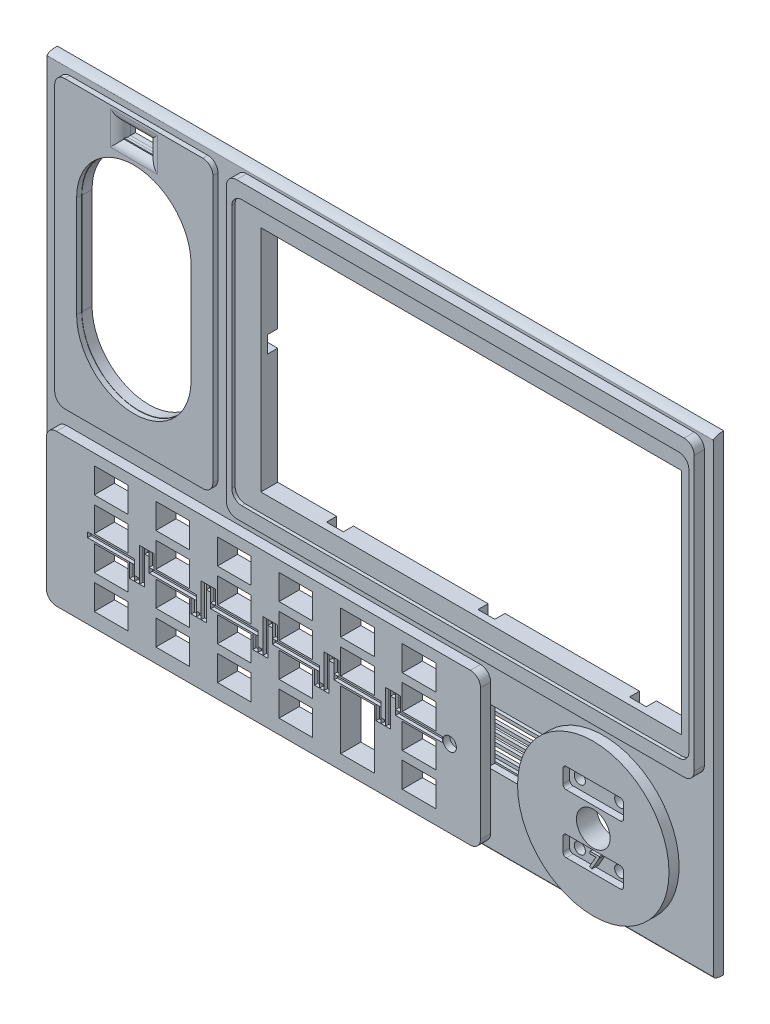
SolidWorks part; units mm, degrees
ref_plane "Front Plane" through (0, 0, 0) normal (0, 0, 1) x (1, 0, 0)
ref_plane "Top Plane" through (0, 0, 0) normal (0, 1, 0) x (1, 0, 0)
ref_plane "Right Plane" through (0, 0, 0) normal (1, 0, 0) x (0, 0, -1)
sketch "Sketch1" plane through (0, 0, 0) normal (0, 0, 1) x (1, 0, 0)
  line L1 (99, -70) -> (-99, -70)
  line L2 (99, -70) -> (99, 70)
  line L3 (99, 70) -> (-99, 70)
  line L4 (-99, -70) -> (-99, 70)
  line L5 (99, -70) -> (-99, 70) construction
  line L6 (99, 70) -> (-99, -70) construction
  point P0 (0, 0)
  dimension "D1" = 198
  dimension "D2" = 140
extrude "main_body" add sketch "Sketch1" along normal blind 3
fillet "long_corners" radius 3 2 edges at (0, 70, 3) (0, -70, 3) second distance 1 first distance on face at (0, 70, 1.5) first distance on face at (0, -70, 1.5)
sketch "Sketch2" plane through (0, 0, 3) normal (0, 0, 1) x (1, 0, 0)
  line L0 (-99, 24.75) -> (99, 24.75) construction
  line L1 (-99, 69) -> (-99, -69) construction
  line L2 (99, -69) -> (99, 69) construction
  line L3 (99, 69) -> (-99, 69) construction
  line L4 (-48.25, -17.75) -> (-95.25, -17.75)
  line L5 (-48.25, -17.75) -> (-48.25, 67.25)
  line L6 (-48.25, 67.25) -> (-95.25, 67.25)
  line L7 (-95.25, -17.75) -> (-95.25, 67.25)
  line L8 (-48.25, -17.75) -> (-95.25, 67.25) construction
  line L9 (-48.25, 67.25) -> (-95.25, -17.75) construction
  point P6 (-71.75, 24.75)
  dimension "D1" = 85
  dimension "D2" = 47
  dimension "D3" = 27.25
  dimension "D4" = 44.25
extrude "speaker" add sketch "Sketch2" along normal blind 1.5
fillet "speaker_corners" radius 3 4 edges at (-95.25, 67.25, 3.75) (-95.25, -17.75, 3.75) (-48.25, -17.75, 3.75) (-48.25, 67.25, 3.75)
sketch "Sketch19" plane through (0, 0, 4.5) normal (0, 0, 1) x (1, 0, 0)
  line L0 (-71.75, 67.25) -> (-71.75, -17.75) construction
  line L1 (-51.25, 67.25) -> (-92.25, 67.25) construction
  line L2 (-92.25, -17.75) -> (-51.25, -17.75) construction
  line L3 (-71.75, 8.25) -> (-71.75, 38.25) construction
  line L4 (-95.25, 64.25) -> (-95.25, -14.75) construction
  line L5 (-95.25, 24.75) -> (-48.25, 24.75) construction
  line L6 (-48.25, -14.75) -> (-48.25, 64.25) construction
  line L7 (-88.75, 8.25) -> (-88.75, 38.25)
  line L8 (-54.75, 8.25) -> (-54.75, 38.25)
  arc A0 (-88.75, 8.25) -> (-54.75, 8.25) centre (-71.75, 8.25) ccw
  arc A1 (-54.75, 38.25) -> (-88.75, 38.25) centre (-71.75, 38.25) ccw
  point P14 (-71.75, 23.25)
  point P19 (-71.75, -8.75)
  point P20 (-71.75, 55.25)
  dimension "D2" = 64
  dimension "D1" = 34
  dimension "D3" = 12
extrude "speaker_cut" cut sketch "Sketch19" against normal through all
sketch "Sketch21" plane through (0, 0, 0) normal (0, 0, -1) x (-1, 0, 0)
  line L0 (71.75, -8.75) -> (71.75, 55.25) construction
  line L2 (54.75, 8.25) -> (54.75, 38.25) construction
  line L3 (54.75, 23.25) -> (88.75, 23.25) construction
  line L4 (88.75, 38.25) -> (88.75, 8.25) construction
  line L5 (50.25, 59.25) -> (93.25, 59.25)
  line L6 (50.25, 59.25) -> (50.25, -12.75)
  line L7 (50.25, -12.75) -> (93.25, -12.75)
  line L8 (93.25, 59.25) -> (93.25, -12.75)
  line L9 (50.25, 59.25) -> (93.25, -12.75) construction
  line L10 (50.25, -12.75) -> (93.25, 59.25) construction
  arc A0 (54.75, 8.25) -> (88.75, 8.25) centre (71.75, 8.25) ccw construction
  arc A1 (88.75, 38.25) -> (54.75, 38.25) centre (71.75, 38.25) ccw construction
  point P14 (71.75, 23.25)
  dimension "D1" = 43
  dimension "D2" = 72
extrude "speaker_slot" cut sketch "Sketch21" against normal blind 3
sketch "Sketch36" plane through (0, 0, 3) normal (0, 0, -1) x (-1, 0, 0)
  line L0 (50.25, 23.25) -> (93.25, 23.25) construction
  line L1 (50.25, 59.25) -> (50.25, -12.75) construction
  line L2 (71.75, 8.2639) -> (71.75, 38.2361) construction
  line L3 (71.75, 8.2639) -> (71.75, 38.2361) construction
  line L4 (93.25, -12.75) -> (93.25, 59.25) construction
  line L5 (50.25, 59.25) -> (50.25, -12.75) construction
  line L6 (54.8316, 8.2639) -> (54.8316, 38.2361)
  line L9 (88.6684, 8.2639) -> (88.6684, 38.2361)
  line L10 (54.25, 8.2639) -> (54.25, 38.2361)
  line L11 (89.25, 8.2639) -> (89.25, 38.2361)
  line L12 (93.25, 59.25) -> (50.25, 59.25) construction
  line L13 (71.75, 59.25) -> (71.75, -12.75) construction
  line L14 (50.25, -12.75) -> (93.25, -12.75) construction
  line L23 (50.25, 57.25) -> (93.25, 57.25)
  line L25 (50.25, 57.25) -> (50.25, 56.75)
  line L26 (93.25, -0.25) -> (87.75, -0.25)
  line L27 (50.25, 56.75) -> (93.25, 56.75)
  line L28 (93.25, 57.25) -> (93.25, 56.75)
  line L37 (93.25, -12.75) -> (93.25, 59.25) construction
  line L38 (93.25, -0.25) -> (93.25, 0.25)
  line L39 (93.25, 0.25) -> (87.75, 0.25)
  line L48 (93.25, -10.75) -> (50.25, -10.75)
  line L49 (93.25, -10.75) -> (93.25, -10.25)
  line L50 (93.25, -10.25) -> (50.25, -10.25)
  line L51 (50.25, -10.75) -> (50.25, -10.25)
  line L52 (93.25, 46.75) -> (87.75, 46.75)
  line L53 (93.25, 46.75) -> (93.25, 46.25)
  line L54 (93.25, 46.25) -> (87.75, 46.25)
  line L55 (87.75, 46.75) -> (87.75, 46.25)
  line L56 (93.25, 35.25) -> (89.75, 35.25)
  line L57 (93.25, 35.25) -> (93.25, 34.75)
  line L58 (93.25, 34.75) -> (89.75, 34.75)
  line L59 (89.75, 35.25) -> (89.75, 34.75)
  line L60 (93.25, 23.25) -> (89.75, 23.25)
  line L61 (93.25, 23.25) -> (93.25, 23.75)
  line L62 (93.25, 23.75) -> (89.75, 23.75)
  line L63 (89.75, 23.25) -> (89.75, 23.75)
  line L64 (93.25, 10.75) -> (89.75, 10.75)
  line L65 (93.25, 10.75) -> (93.25, 11.25)
  line L66 (93.25, 11.25) -> (89.75, 11.25)
  line L67 (89.75, 10.75) -> (89.75, 11.25)
  line L68 (87.75, -0.25) -> (87.75, 0.25)
  line L69 (93.25, -5.25) -> (83.25, -5.25)
  line L70 (93.25, -5.25) -> (93.25, -5.75)
  line L71 (93.25, -5.75) -> (83.25, -5.75)
  line L72 (83.25, -5.25) -> (83.25, -5.75)
  line L73 (93.25, 52.25) -> (83.25, 52.25)
  line L74 (93.25, 52.25) -> (93.25, 51.75)
  line L75 (93.25, 51.75) -> (83.25, 51.75)
  line L76 (83.25, 52.25) -> (83.25, 51.75)
  line L77 (50.25, 52.25) -> (60.25, 52.25)
  line L78 (50.25, 52.25) -> (50.25, 51.75)
  line L79 (50.25, 51.75) -> (60.25, 51.75)
  line L80 (60.25, 52.25) -> (60.25, 51.75)
  line L81 (50.25, 46.75) -> (55.75, 46.75)
  line L82 (50.25, 46.75) -> (50.25, 46.25)
  line L83 (50.25, 46.25) -> (55.75, 46.25)
  line L84 (55.75, 46.75) -> (55.75, 46.25)
  line L85 (50.25, 35.25) -> (53.75, 35.25)
  line L86 (50.25, 35.25) -> (50.25, 34.75)
  line L87 (50.25, 34.75) -> (53.75, 34.75)
  line L88 (53.75, 35.25) -> (53.75, 34.75)
  line L89 (50.25, 23.25) -> (53.75, 23.25)
  line L90 (50.25, 23.25) -> (50.25, 23.75)
  line L91 (50.25, 23.75) -> (53.75, 23.75)
  line L92 (53.75, 23.25) -> (53.75, 23.75)
  line L93 (50.25, 10.25) -> (53.75, 10.25)
  line L94 (50.25, 10.25) -> (50.25, 10.75)
  line L95 (50.25, 10.75) -> (53.75, 10.75)
  line L96 (53.75, 10.25) -> (53.75, 10.75)
  line L97 (50.25, -0.25) -> (55.75, -0.25)
  line L98 (50.25, -0.25) -> (50.25, 0.25)
  line L99 (50.25, 0.25) -> (55.75, 0.25)
  line L100 (55.75, -0.25) -> (55.75, 0.25)
  line L101 (50.25, -5.25) -> (60.25, -5.25)
  line L102 (50.25, -5.25) -> (50.25, -5.75)
  line L103 (50.25, -5.75) -> (60.25, -5.75)
  line L104 (60.25, -5.25) -> (60.25, -5.75)
  arc A0 (54.25, 8.2639) -> (89.25, 8.2639) centre (71.75, 8.2639) ccw
  arc A1 (89.25, 38.2361) -> (54.25, 38.2361) centre (71.75, 38.2361) ccw
  arc A4 (54.8316, 8.2639) -> (88.6684, 8.2639) centre (71.75, 8.2639) ccw
  arc A5 (88.6684, 38.2361) -> (54.8316, 38.2361) centre (71.75, 38.2361) ccw
  point P6 (71.75, 23.25)
  point P22 (71.75, 23.25)
  point P31 (89.25, 23.25)
  point P32 (71.75, 55.1546)
  point P33 (71.75, -8.6546)
  point P95 (52, 35.25)
  point P96 (55.25, 51.75)
  point P97 (91.5, 10.75)
  dimension "D48" = 0.5816
  dimension "D1" = 33.8368
  dimension "D2" = 35
  dimension "D3" = 63.8091
  dimension "D4" = 0.5
  dimension "D5" = 0.5
  dimension "D6" = 0.5
  dimension "D7" = 0.5
  dimension "D8" = 0.5
  dimension "D9" = 11
  dimension "D10" = 11
  dimension "D11" = 5
  dimension "D12" = 4.5
  dimension "D13" = 10
  dimension "D14" = 5.5
  dimension "D15" = 3.5
  dimension "D16" = 3.5
  dimension "D17" = 0.5
  dimension "D18" = 0.5
  dimension "D19" = 0.5
  dimension "D20" = 0.5
  dimension "D21" = 11
  dimension "D22" = 11
  dimension "D23" = 5
  dimension "D24" = 10
  dimension "D25" = 5.5
  dimension "D26" = 3.5
  dimension "D27" = 3.5
  dimension "D28" = 0.5
  dimension "D29" = 0.5
  dimension "D30" = 0.5
  dimension "D31" = 0.5
  dimension "D32" = 0.5
  dimension "D33" = 0.5
  dimension "D34" = 0.5
  dimension "D35" = 12
  dimension "D36" = 10.5
  dimension "D37" = 5.5
  dimension "D38" = 5
  dimension "D39" = 4.5
  dimension "D40" = 3.5
  dimension "D41" = 10
  dimension "D42" = 4.5
  dimension "D43" = 5
  dimension "D44" = 10
  dimension "D45" = 3.5
  dimension "D46" = 5.5
  dimension "D47" = 10
extrude "speaker_print_support" add sketch "Sketch36" along normal blind 3
sketch "Sketch3" plane through (0, 0, 3) normal (0, 0, 1) x (1, 0, 0)
  line L0 (-99, 24.625) -> (99, 24.625) construction
  line L1 (-99, 69) -> (-99, -69) construction
  line L2 (99, -69) -> (99, 69) construction
  line L4 (-48.25, -14.75) -> (-48.25, 64.25) construction
  line L5 (96.25, -19) -> (-42.75, -19)
  line L6 (96.25, -19) -> (96.25, 68.25)
  line L7 (96.25, 68.25) -> (-42.75, 68.25)
  line L8 (-42.75, -19) -> (-42.75, 68.25)
  line L9 (96.25, -19) -> (-42.75, 68.25) construction
  line L10 (96.25, 68.25) -> (-42.75, -19) construction
  line L11 (99, 70) -> (-99, 70) construction
  point P8 (26.75, 24.625)
  dimension "D1" = 1.75
  dimension "D2" = 87.25
  dimension "D3" = 139
  dimension "D4" = 2.75
  dimension "D5" = 5.5
extrude "lcd" add sketch "Sketch3" along normal blind 3
fillet "lcd_corners" radius 3 4 edges at (96.25, -19, 4.5) (-42.75, -19, 4.5) (96.25, 68.25, 4.5) (-42.75, 68.25, 4.5)
sketch "Sketch9" plane through (0, 0, 6) normal (0, 0, 1) x (1, 0, 0)
  line L0 (-42.75, 24.5) -> (96.25, 24.5) construction
  line L1 (-42.75, 65.25) -> (-42.75, -16) construction
  line L2 (96.25, -16) -> (96.25, 65.25) construction
  line L3 (-39.75, -19) -> (93.25, -19) construction
  line L4 (94.65, -14.875) -> (-41.15, -14.875)
  line L5 (94.65, -14.875) -> (94.65, 63.875)
  line L6 (94.65, 63.875) -> (-41.15, 63.875)
  line L7 (-41.15, -14.875) -> (-41.15, 63.875)
  line L8 (94.65, -14.875) -> (-41.15, 63.875) construction
  line L9 (94.65, 63.875) -> (-41.15, -14.875) construction
  line L10 (93.25, 68.25) -> (-39.75, 68.25) construction
  line L11 (96.25, -16) -> (96.25, 65.25) construction
  point P6 (26.75, 24.5)
  dimension "D1" = 135.8
  dimension "D2" = 78.75
  dimension "D3" = 1.6
  dimension "D4" = 4.125
  dimension "D5" = 4.375
  dimension "D6" = 1.6
extrude "lcd_front" cut sketch "Sketch9" against normal blind 1
fillet "lcd_front_corners" radius 3 4 edges at (94.65, -14.875, 5.5) (94.65, 63.875, 5.5) (-41.15, 63.875, 5.5) (-41.15, -14.875, 5.5)
sketch "Sketch10" plane through (0, 0, 0) normal (0, 0, -1) x (-1, 0, 0)
  line L0 (-94.65, -11.875) -> (-94.65, 60.875) construction
  line L1 (-91.65, 63.875) -> (38.15, 63.875) construction
  line L2 (41.15, 63.875) -> (41.15, -14.875) construction
  line L3 (-94.65, 63.875) -> (41.15, 63.875) construction
  line L4 (33.5, -9.5) -> (-91.5, -9.5)
  line L5 (33.5, -9.5) -> (33.5, 58.5)
  line L6 (33.5, 58.5) -> (-91.5, 58.5)
  line L7 (-91.5, -9.5) -> (-91.5, 58.5)
  line L8 (-91.5, -9.5) -> (33.5, 58.5) construction
  line L9 (-91.5, 58.5) -> (33.5, -9.5) construction
  line L10 (-99, -70) -> (-99, 70) construction
  line L11 (-99, 70) -> (99, 70) construction
  line L13 (38.15, -14.875) -> (-91.65, -14.875) construction
  dimension "D1" = 125
  dimension "D2" = 68
  dimension "D3" = 7.5
  dimension "D4" = 7.65
  dimension "D5" = 11.5
  dimension "D6" = 5.375
  dimension "D7" = 3.15
  dimension "D8" = 5.375
  dimension "D9" = 5.375
extrude "lcd_back" cut sketch "Sketch10" against normal through all
sketch "Sketch56" plane through (0, 0, 0) normal (0, 0, -1) x (-1, 0, 0)
  line L0 (-91.5, -9.5) -> (33.5, -9.5) construction
  line L1 (-79, -9.5) -> (-74, -9.5)
  line L2 (-79, -9.5) -> (-79, -12.5)
  line L3 (-79, -12.5) -> (-74, -12.5)
  line L4 (-74, -9.5) -> (-74, -12.5)
  line L5 (33.5, 58.5) -> (-91.5, 58.5) construction
  line L6 (-34, -9.5) -> (-29, -9.5)
  line L7 (-34, -9.5) -> (-34, -12.5)
  line L8 (-34, -12.5) -> (-29, -12.5)
  line L9 (-29, -9.5) -> (-29, -12.5)
  line L10 (11, -9.5) -> (16, -9.5)
  line L11 (11, -9.5) -> (11, -12.5)
  line L12 (11, -12.5) -> (16, -12.5)
  line L13 (16, -9.5) -> (16, -12.5)
  line L14 (-79, 58.5) -> (-74, 58.5)
  line L15 (-79, 58.5) -> (-79, 61.5)
  line L16 (-79, 61.5) -> (-74, 61.5)
  line L17 (-74, 58.5) -> (-74, 61.5)
  line L18 (33.5, -9.5) -> (33.5, 58.5) construction
  line L19 (-34, 58.5) -> (-29, 58.5)
  line L20 (-34, 58.5) -> (-34, 61.5)
  line L21 (-34, 61.5) -> (-29, 61.5)
  line L22 (-29, 58.5) -> (-29, 61.5)
  line L23 (11, 58.5) -> (16, 58.5)
  line L24 (11, 58.5) -> (11, 61.5)
  line L25 (11, 61.5) -> (16, 61.5)
  line L26 (16, 58.5) -> (16, 61.5)
  line L27 (33.5, 30) -> (36.5, 30)
  line L28 (33.5, 30) -> (33.5, 25)
  line L29 (33.5, 25) -> (36.5, 25)
  line L30 (36.5, 30) -> (36.5, 25)
  line L31 (-99, -70) -> (-99, 70) construction
  line L32 (-99, 70) -> (99, 70) construction
  point P34 (-29, -11)
  dimension "D1" = 5
  dimension "D2" = 5
  dimension "D3" = 5
  dimension "D4" = 5
  dimension "D5" = 5
  dimension "D6" = 5
  dimension "D7" = 5
  dimension "D8" = 3
  dimension "D9" = 3
  dimension "D10" = 3
  dimension "D11" = 3
  dimension "D12" = 3
  dimension "D13" = 3
  dimension "D14" = 3
  dimension "D15" = 40
  dimension "D16" = 40
  dimension "D17" = 20
  dimension "D18" = 20
  dimension "D19" = 40
  dimension "D20" = 40
  dimension "D21" = 40
extrude "lcd_glue_points" cut sketch "Sketch56" against normal blind 3
sketch "Sketch4" plane through (0, 0, 3) normal (0, 0, 1) x (1, 0, 0)
  line L0 (-99, -45.75) -> (99, -45.75) construction
  line L1 (-99, 69) -> (-99, -69) construction
  line L2 (99, -69) -> (99, 69) construction
  line L4 (-92.25, -17.75) -> (-51.25, -17.75) construction
  line L5 (32.75, -68.25) -> (-96.25, -68.25)
  line L6 (32.75, -68.25) -> (32.75, -23.25)
  line L7 (32.75, -23.25) -> (-96.25, -23.25)
  line L8 (-96.25, -68.25) -> (-96.25, -23.25)
  line L9 (32.75, -68.25) -> (-96.25, -23.25) construction
  line L10 (32.75, -23.25) -> (-96.25, -68.25) construction
  line L11 (-99, -70) -> (99, -70) construction
  point P8 (-31.75, -45.75)
  dimension "D1" = 1.75
  dimension "D2" = 129
  dimension "D3" = 45
  dimension "D4" = 2.75
  dimension "D5" = 5.5
extrude "keypad" add sketch "Sketch4" along normal blind 3
fillet "keypad_corners" radius 3 4 edges at (-96.25, -68.25, 4.5) (32.75, -68.25, 4.5) (32.75, -23.25, 4.5) (-96.25, -23.25, 4.5)
sketch "Sketch25" plane through (0, 0, 6) normal (0, 0, 1) x (1, 0, 0)
  line L0 (-96.25, -30.25) -> (32.75, -30.25) construction
  line L1 (29.75, -23.25) -> (-93.25, -23.25) construction
  line L2 (-93.25, -68.25) -> (29.75, -68.25) construction
  line L3 (-77, -23.25) -> (-77, -68.25) construction
  line L5 (-35.4, -64) -> (32.75, -64) construction
  line L6 (-96.25, -26.25) -> (-96.25, -65.25) construction
  line L11 (32.75, -65.25) -> (32.75, -26.25) construction
  line L12 (-58.7, -23.25) -> (-58.7, -68.25) construction
  line L13 (-96.25, -40.25) -> (32.75, -40.25) construction
  line L14 (29.75, -23.25) -> (-93.25, -23.25) construction
  line L15 (-40.4, -23.25) -> (-40.4, -68.25) construction
  line L16 (-93.25, -68.25) -> (29.75, -68.25) construction
  line L17 (-72, -34) -> (-82, -34)
  line L18 (-22.1, -23.25) -> (-22.1, -68.25) construction
  line L19 (-96.25, -50.25) -> (32.75, -50.25) construction
  line L20 (-3.8, -23.25) -> (-3.8, -68.25) construction
  line L21 (-72, -34) -> (-72, -26.5)
  line L22 (14.5, -23.25) -> (14.5, -68.25) construction
  line L23 (-96.25, -26.25) -> (-96.25, -65.25) construction
  line L24 (-96.25, -60.25) -> (32.75, -60.25) construction
  line L25 (-72, -26.5) -> (-82, -26.5)
  line L26 (-82, -34) -> (-82, -26.5)
  line L27 (-72, -34) -> (-82, -26.5) construction
  line L28 (-72, -26.5) -> (-82, -34) construction
  line L29 (-72, -44) -> (-82, -44)
  line L30 (-72, -44) -> (-72, -36.5)
  line L31 (-72, -36.5) -> (-82, -36.5)
  line L32 (-82, -44) -> (-82, -36.5)
  line L33 (-72, -44) -> (-82, -36.5) construction
  line L34 (-72, -36.5) -> (-82, -44) construction
  line L35 (-72, -54) -> (-82, -54)
  line L36 (-72, -54) -> (-72, -46.5)
  line L37 (-72, -46.5) -> (-82, -46.5)
  line L38 (-82, -54) -> (-82, -46.5)
  line L39 (-72, -54) -> (-82, -46.5) construction
  line L40 (-72, -46.5) -> (-82, -54) construction
  line L41 (-72, -64) -> (-82, -64)
  line L42 (-72, -64) -> (-72, -56.5)
  line L43 (-72, -56.5) -> (-82, -56.5)
  line L44 (-82, -64) -> (-82, -56.5)
  line L45 (-72, -64) -> (-82, -56.5) construction
  line L46 (-72, -56.5) -> (-82, -64) construction
  line L47 (-53.7, -34) -> (-63.7, -34)
  line L48 (-53.7, -34) -> (-53.7, -26.5)
  line L49 (-53.7, -26.5) -> (-63.7, -26.5)
  line L50 (-63.7, -34) -> (-63.7, -26.5)
  line L51 (-53.7, -34) -> (-63.7, -26.5) construction
  line L52 (-53.7, -26.5) -> (-63.7, -34) construction
  line L53 (-53.7, -44) -> (-63.7, -44)
  line L54 (-53.7, -44) -> (-53.7, -36.5)
  line L55 (-53.7, -36.5) -> (-63.7, -36.5)
  line L56 (-63.7, -44) -> (-63.7, -36.5)
  line L57 (-53.7, -44) -> (-63.7, -36.5) construction
  line L58 (-53.7, -36.5) -> (-63.7, -44) construction
  line L59 (-53.7, -54) -> (-63.7, -54)
  line L60 (-53.7, -54) -> (-53.7, -46.5)
  line L61 (-53.7, -46.5) -> (-63.7, -46.5)
  line L62 (-63.7, -54) -> (-63.7, -46.5)
  line L63 (-53.7, -54) -> (-63.7, -46.5) construction
  line L64 (-53.7, -46.5) -> (-63.7, -54) construction
  line L65 (-53.7, -64) -> (-63.7, -64)
  line L66 (-53.7, -64) -> (-53.7, -56.5)
  line L67 (-53.7, -56.5) -> (-63.7, -56.5)
  line L68 (-63.7, -64) -> (-63.7, -56.5)
  line L69 (-53.7, -64) -> (-63.7, -56.5) construction
  line L70 (-53.7, -56.5) -> (-63.7, -64) construction
  line L71 (-35.4, -34) -> (-45.4, -34)
  line L72 (-35.4, -34) -> (-35.4, -26.5)
  line L73 (-35.4, -26.5) -> (-45.4, -26.5)
  line L74 (-45.4, -34) -> (-45.4, -26.5)
  line L75 (-35.4, -34) -> (-45.4, -26.5) construction
  line L76 (-35.4, -26.5) -> (-45.4, -34) construction
  line L77 (-35.4, -44) -> (-45.4, -44)
  line L78 (-35.4, -44) -> (-35.4, -36.5)
  line L79 (-35.4, -36.5) -> (-45.4, -36.5)
  line L80 (-45.4, -44) -> (-45.4, -36.5)
  line L81 (-35.4, -44) -> (-45.4, -36.5) construction
  line L82 (-35.4, -36.5) -> (-45.4, -44) construction
  line L83 (-35.4, -54) -> (-45.4, -54)
  line L84 (-35.4, -54) -> (-35.4, -46.5)
  line L85 (-35.4, -46.5) -> (-45.4, -46.5)
  line L86 (-45.4, -54) -> (-45.4, -46.5)
  line L87 (-35.4, -54) -> (-45.4, -46.5) construction
  line L88 (-35.4, -46.5) -> (-45.4, -54) construction
  line L89 (-35.4, -64) -> (-45.4, -64)
  line L90 (-35.4, -64) -> (-35.4, -56.5)
  line L91 (-35.4, -56.5) -> (-45.4, -56.5)
  line L92 (-45.4, -64) -> (-45.4, -56.5)
  line L93 (-35.4, -64) -> (-45.4, -56.5) construction
  line L94 (-35.4, -56.5) -> (-45.4, -64) construction
  line L95 (-17.1, -34) -> (-27.1, -34)
  line L96 (-17.1, -34) -> (-17.1, -26.5)
  line L97 (-17.1, -26.5) -> (-27.1, -26.5)
  line L98 (-27.1, -34) -> (-27.1, -26.5)
  line L99 (-17.1, -34) -> (-27.1, -26.5) construction
  line L100 (-17.1, -26.5) -> (-27.1, -34) construction
  line L101 (-17.1, -44) -> (-27.1, -44)
  line L102 (-17.1, -44) -> (-17.1, -36.5)
  line L103 (-17.1, -36.5) -> (-27.1, -36.5)
  line L104 (-27.1, -44) -> (-27.1, -36.5)
  line L105 (-17.1, -44) -> (-27.1, -36.5) construction
  line L106 (-17.1, -36.5) -> (-27.1, -44) construction
  line L111 (-17.1, -54) -> (-27.1, -54)
  line L112 (-17.1, -54) -> (-17.1, -46.5)
  line L113 (-17.1, -46.5) -> (-27.1, -46.5)
  line L114 (-27.1, -54) -> (-27.1, -46.5)
  line L115 (-17.1, -54) -> (-27.1, -46.5) construction
  line L116 (-17.1, -46.5) -> (-27.1, -54) construction
  line L117 (-17.1, -64) -> (-27.1, -64)
  line L118 (-17.1, -64) -> (-17.1, -56.5)
  line L119 (-17.1, -56.5) -> (-27.1, -56.5)
  line L120 (-27.1, -64) -> (-27.1, -56.5)
  line L121 (-17.1, -64) -> (-27.1, -56.5) construction
  line L122 (-17.1, -56.5) -> (-27.1, -64) construction
  line L127 (1.2, -34) -> (-8.8, -34)
  line L128 (1.2, -34) -> (1.2, -26.5)
  line L129 (1.2, -26.5) -> (-8.8, -26.5)
  line L130 (-8.8, -34) -> (-8.8, -26.5)
  line L131 (1.2, -34) -> (-8.8, -26.5) construction
  line L132 (1.2, -26.5) -> (-8.8, -34) construction
  line L133 (19.5, -34) -> (9.5, -34)
  line L134 (19.5, -34) -> (19.5, -26.5)
  line L135 (19.5, -26.5) -> (9.5, -26.5)
  line L136 (9.5, -34) -> (9.5, -26.5)
  line L137 (19.5, -34) -> (9.5, -26.5) construction
  line L138 (19.5, -26.5) -> (9.5, -34) construction
  line L139 (1.2, -44) -> (-8.8, -44)
  line L140 (1.2, -44) -> (1.2, -36.5)
  line L141 (1.2, -36.5) -> (-8.8, -36.5)
  line L142 (-8.8, -44) -> (-8.8, -36.5)
  line L143 (1.2, -44) -> (-8.8, -36.5) construction
  line L144 (1.2, -36.5) -> (-8.8, -44) construction
  line L145 (19.5, -44) -> (9.5, -44)
  line L146 (19.5, -44) -> (19.5, -36.5)
  line L147 (19.5, -36.5) -> (9.5, -36.5)
  line L148 (9.5, -44) -> (9.5, -36.5)
  line L149 (19.5, -44) -> (9.5, -36.5) construction
  line L150 (19.5, -36.5) -> (9.5, -44) construction
  line L151 (19.5, -54) -> (9.5, -54)
  line L152 (19.5, -54) -> (19.5, -46.5)
  line L153 (19.5, -46.5) -> (9.5, -46.5)
  line L154 (9.5, -54) -> (9.5, -46.5)
  line L155 (19.5, -54) -> (9.5, -46.5) construction
  line L156 (19.5, -46.5) -> (9.5, -54) construction
  line L157 (19.5, -64) -> (9.5, -64)
  line L158 (19.5, -64) -> (19.5, -56.5)
  line L159 (19.5, -56.5) -> (9.5, -56.5)
  line L160 (9.5, -64) -> (9.5, -56.5)
  line L161 (19.5, -64) -> (9.5, -56.5) construction
  line L162 (19.5, -56.5) -> (9.5, -64) construction
  line L163 (1.2, -64) -> (-8.8, -64)
  line L164 (1.2, -64) -> (1.2, -46.5)
  line L165 (1.2, -46.5) -> (-8.8, -46.5)
  line L166 (-8.8, -64) -> (-8.8, -46.5)
  line L167 (1.2, -64) -> (-8.8, -46.5) construction
  line L168 (1.2, -46.5) -> (-8.8, -64) construction
  point P34 (-77, -30.25)
  point P39 (-77, -40.25)
  point P44 (-77, -50.25)
  point P49 (-77, -60.25)
  point P54 (-58.7, -30.25)
  point P59 (-58.7, -40.25)
  point P64 (-58.7, -50.25)
  point P69 (-58.7, -60.25)
  point P74 (-40.4, -30.25)
  point P79 (-40.4, -40.25)
  point P84 (-40.4, -50.25)
  point P89 (-40.4, -60.25)
  point P94 (-22.1, -30.25)
  point P99 (-22.1, -40.25)
  point P104 (-22.1, -50.25)
  point P109 (-22.1, -60.25)
  point P114 (-3.8, -30.25)
  point P119 (14.5, -30.25)
  point P124 (-3.8, -40.25)
  point P129 (14.5, -40.25)
  point P134 (14.5, -50.25)
  point P139 (14.5, -60.25)
  point P144 (-3.8, -55.25)
  dimension "D1" = 18.25
  dimension "D2" = 18.3
  dimension "D3" = 18.3
  dimension "D4" = 18.3
  dimension "D5" = 18.3
  dimension "D6" = 18.3
  dimension "D7" = 19.25
  dimension "D8" = 7
  dimension "D9" = 10
  dimension "D10" = 10
  dimension "D11" = 10
  dimension "D12" = 8
  dimension "D13" = 10
  dimension "D14" = 10
  dimension "D15" = 10
  dimension "D16" = 10
  dimension "D17" = 10
  dimension "D18" = 10
  dimension "D19" = 10
  dimension "D20" = 10
  dimension "D21" = 10
  dimension "D22" = 10
  dimension "D23" = 10
  dimension "D24" = 10
  dimension "D25" = 10
  dimension "D26" = 10
  dimension "D27" = 10
  dimension "D28" = 10
  dimension "D29" = 10
  dimension "D30" = 10
  dimension "D31" = 10
  dimension "D32" = 10
  dimension "D33" = 10
  dimension "D34" = 10
  dimension "D35" = 10
  dimension "D36" = 7.5
  dimension "D37" = 7.5
  dimension "D38" = 7.5
  dimension "D39" = 7.5
  dimension "D40" = 7.5
  dimension "D41" = 7.5
  dimension "D42" = 17.5
  dimension "D43" = 7.5
  dimension "D44" = 7.5
  dimension "D45" = 7.5
  dimension "D46" = 7.5
  dimension "D47" = 7.5
  dimension "D48" = 7.5
  dimension "D49" = 7.5
  dimension "D50" = 7.5
  dimension "D51" = 7.5
  dimension "D52" = 7.5
  dimension "D53" = 7.5
  dimension "D54" = 7.5
  dimension "D55" = 7.5
  dimension "D56" = 7.5
  dimension "D57" = 7.5
  dimension "D58" = 7.5
  dimension "D59" = 5
extrude "keypad_cuts_0.8" cut sketch "Sketch25" against normal through all
sketch "Sketch40" plane through (0, 0, 6) normal (0, 0, 1) x (1, 0, 0)
  line L0 (16.75, -23.25) -> (16.75, -68.25) construction
  line L1 (-8.25, -23.25) -> (-8.25, -68.25) construction
  line L2 (-67.25, -23.25) -> (-67.25, -68.25) construction
  line L3 (-96.25, -45.75) -> (32.75, -45.75) construction
  line L4 (-83.25, -23.25) -> (-83.25, -68.25) construction
  line L5 (29.75, -23.25) -> (-93.25, -23.25) construction
  line L6 (-93.25, -68.25) -> (29.75, -68.25) construction
  line L11 (-77.25, -49.75) -> (-89.25, -49.75)
  line L12 (-77.25, -49.75) -> (-77.25, -41.75)
  line L13 (-93.25, -68.25) -> (29.75, -68.25) construction
  line L14 (-77.25, -41.75) -> (-89.25, -41.75)
  line L15 (-89.25, -49.75) -> (-89.25, -41.75)
  line L16 (-35.25, -68.25) -> (-35.25, -23.25) construction
  line L18 (29.75, -23.25) -> (-93.25, -23.25) construction
  line L19 (-77.25, -49.75) -> (-89.25, -41.75) construction
  line L20 (-51.25, -68.25) -> (-51.25, -23.25) construction
  line L22 (-77.25, -41.75) -> (-89.25, -49.75) construction
  line L23 (-61.25, -49.75) -> (-73.25, -49.75)
  line L24 (-61.25, -49.75) -> (-61.25, -41.75)
  line L25 (-61.25, -41.75) -> (-73.25, -41.75)
  line L26 (-73.25, -49.75) -> (-73.25, -41.75)
  line L27 (-61.25, -49.75) -> (-73.25, -41.75) construction
  line L28 (-61.25, -41.75) -> (-73.25, -49.75) construction
  line L29 (-45.25, -49.75) -> (-57.25, -49.75)
  line L30 (-45.25, -49.75) -> (-45.25, -41.75)
  line L31 (-45.25, -41.75) -> (-57.25, -41.75)
  line L32 (-57.25, -49.75) -> (-57.25, -41.75)
  line L33 (-45.25, -49.75) -> (-57.25, -41.75) construction
  line L34 (-45.25, -41.75) -> (-57.25, -49.75) construction
  line L35 (-29.25, -49.75) -> (-41.25, -49.75)
  line L36 (-29.25, -49.75) -> (-29.25, -41.75)
  line L37 (-29.25, -41.75) -> (-41.25, -41.75)
  line L38 (-41.25, -49.75) -> (-41.25, -41.75)
  line L39 (-29.25, -49.75) -> (-41.25, -41.75) construction
  line L40 (-29.25, -41.75) -> (-41.25, -49.75) construction
  line L45 (-2.25, -41.75) -> (-14.25, -41.75)
  line L46 (-2.25, -41.75) -> (-2.25, -33.75)
  line L51 (-2.25, -33.75) -> (-14.25, -33.75)
  line L52 (-14.25, -41.75) -> (-14.25, -33.75)
  line L53 (22.75, -35.75) -> (10.75, -35.75)
  line L54 (22.75, -35.75) -> (22.75, -27.75)
  line L55 (22.75, -27.75) -> (10.75, -27.75)
  line L56 (10.75, -35.75) -> (10.75, -27.75)
  line L57 (22.75, -35.75) -> (10.75, -27.75) construction
  line L58 (22.75, -27.75) -> (10.75, -35.75) construction
  line L59 (22.75, -63.75) -> (10.75, -63.75)
  line L60 (22.75, -63.75) -> (22.75, -55.75)
  line L61 (22.75, -55.75) -> (10.75, -55.75)
  line L62 (10.75, -63.75) -> (10.75, -55.75)
  line L63 (22.75, -63.75) -> (10.75, -55.75) construction
  line L64 (22.75, -55.75) -> (10.75, -63.75) construction
  line L69 (32.75, -65.25) -> (32.75, -26.25) construction
  line L70 (-2.25, -57.25) -> (-14.25, -57.25)
  line L75 (-2.25, -57.25) -> (-2.25, -49.25)
  line L76 (-2.25, -49.25) -> (-14.25, -49.25)
  line L77 (-2.25, -41.75) -> (-14.25, -33.75) construction
  line L78 (-2.25, -33.75) -> (-14.25, -41.75) construction
  line L85 (-14.25, -57.25) -> (-14.25, -49.25)
  line L86 (-2.25, -57.25) -> (-14.25, -49.25) construction
  line L87 (-2.25, -49.25) -> (-14.25, -57.25) construction
  line L88 (-96.25, -26.25) -> (-96.25, -65.25) construction
  line L89 (32.75, -65.25) -> (32.75, -26.25) construction
  line L93 (32.75, -59.75) -> (-96.25, -59.75) construction
  line L94 (-96.25, -31.75) -> (32.75, -31.75) construction
  line L95 (32.75, -31.75) -> (32.75, -37.75) construction
  line L96 (32.75, -37.75) -> (-96.25, -37.75) construction
  line L99 (-96.25, -26.25) -> (-96.25, -65.25) construction
  line L100 (-96.25, -53.75) -> (32.75, -53.75) construction
  point P18 (-83.25, -45.75)
  point P25 (-67.25, -45.75)
  point P30 (-51.25, -45.75)
  point P35 (-35.25, -45.75)
  point P40 (-8.25, -37.75)
  point P45 (-8.25, -53.25)
  point P50 (16.75, -31.75)
  point P55 (16.75, -59.75)
  dimension "D1" = 8
  dimension "D2" = 8
  dimension "D3" = 8
  dimension "D4" = 8
  dimension "D5" = 8
  dimension "D6" = 12
  dimension "D7" = 8
  dimension "D8" = 8
  dimension "D9" = 12
  dimension "D10" = 12
  dimension "D11" = 12
  dimension "D12" = 12
  dimension "D13" = 12
  dimension "D14" = 12
  dimension "D15" = 8
  dimension "D16" = 12
  dimension "D17" = 8
  dimension "D18" = 8
  dimension "D19" = 27
  dimension "D20" = 14
  dimension "D21" = 16
  dimension "D22" = 16
  dimension "D23" = 16
  dimension "D24" = 25
  dimension "D25" = 14
extrude "keypad_cuts_0.7" [suppressed] cut sketch "Sketch40" against normal through all
sketch "Sketch41" [suppressed] plane through (0, 0, 0) normal (0, 0, -1) x (-1, 0, 0)
  line L0 (-22.75, -27.75) -> (-10.75, -35.75) construction
  line L1 (-22.75, -55.75) -> (-10.75, -63.75) construction
  line L2 (8.25, -33.75) -> (8.25, -57.25) construction
  line L3 (-10.75, -63.75) -> (-22.75, -63.75) construction
  line L4 (29.25, -45.75) -> (89.25, -45.75) construction
  line L5 (29.25, -49.75) -> (29.25, -41.75) construction
  line L6 (89.25, -41.75) -> (89.25, -49.75) construction
  line L7 (-6.75, -39.75) -> (-26.75, -39.75)
  line L8 (2.25, -33.75) -> (14.25, -33.75) construction
  line L9 (-6.75, -39.75) -> (-6.75, -23.75)
  line L10 (91.25, -52.75) -> (27.25, -52.75)
  line L11 (-6.75, -23.75) -> (-26.75, -23.75)
  line L12 (14.25, -57.25) -> (2.25, -57.25) construction
  line L13 (-26.75, -39.75) -> (-26.75, -23.75)
  line L14 (-10.75, -55.75) -> (-22.75, -63.75) construction
  line L15 (-6.75, -39.75) -> (-26.75, -23.75) construction
  line L16 (-10.75, -35.75) -> (-22.75, -35.75) construction
  line L17 (-22.75, -35.75) -> (-22.75, -27.75) construction
  line L18 (-22.75, -35.75) -> (-10.75, -27.75) construction
  line L19 (-6.75, -23.75) -> (-26.75, -39.75) construction
  line L21 (-6.75, -67.75) -> (-26.75, -67.75)
  line L22 (16.25, -59.5) -> (0.25, -59.5)
  line L23 (-6.75, -67.75) -> (-6.75, -51.75)
  line L24 (91.25, -52.75) -> (91.25, -38.75)
  line L25 (-6.75, -51.75) -> (-26.75, -51.75)
  line L26 (91.25, -38.75) -> (27.25, -38.75)
  line L27 (-26.75, -67.75) -> (-26.75, -51.75)
  line L28 (27.25, -52.75) -> (27.25, -38.75)
  line L29 (-6.75, -67.75) -> (-26.75, -51.75) construction
  line L30 (91.25, -52.75) -> (27.25, -38.75) construction
  line L31 (-6.75, -51.75) -> (-26.75, -67.75) construction
  line L36 (16.25, -59.5) -> (16.25, -31.5)
  line L37 (16.25, -31.5) -> (0.25, -31.5)
  line L42 (0.25, -59.5) -> (0.25, -31.5)
  line L43 (16.25, -59.5) -> (0.25, -31.5) construction
  line L48 (91.25, -38.75) -> (27.25, -52.75) construction
  line L49 (16.25, -31.5) -> (0.25, -59.5) construction
  point P19 (59.25, -45.75)
  point P44 (8.25, -45.5)
  point P68 (-16.75, -59.75)
  point P69 (-16.75, -31.75)
  dimension "D1" = 20
  dimension "D2" = 20
  dimension "D3" = 16
  dimension "D4" = 16
  dimension "D5" = 16
  dimension "D6" = 28
  dimension "D7" = 64
  dimension "D8" = 14
extrude "keypad_back_0.7" [suppressed] cut sketch "Sketch41" against normal blind 5
sketch "Sketch5" plane through (0, 0, 3) normal (0, 0, 1) x (1, 0, 0)
  line L0 (32.75, -45.75) -> (99, -45.75) construction
  line L1 (32.75, -65.25) -> (32.75, -26.25) construction
  line L2 (99, -69) -> (99, 69) construction
  circle A0 centre (66.25, -45.75) radius 22.5
  dimension "D1" = 45
  dimension "D2" = 32.75
  dimension "D3" = 33.5
extrude "vfo" add sketch "Sketch5" along normal blind 3
sketch "Sketch7" plane through (0, 0, 6) normal (0, 0, 1) x (1, 0, 0)
  line L0 (43.75, -45.75) -> (88.75, -45.75) construction
  line L1 (66.25, -23.25) -> (66.25, -68.25) construction
  circle A0 centre (66.25, -45.75) radius 22.5 construction
  circle A1 centre (66.25, -45.75) radius 22.5 construction
  circle A2 centre (66.25, -45.75) radius 5
  dimension "D1" = 10
extrude "vfo_encoder_knob_cut" cut sketch "Sketch7" against normal through all
sketch "Sketch37" plane through (0, 0, 6) normal (0, 0, 1) x (1, 0, 0)
  line L1 (57.25, -51.25) -> (75.25, -51.25)
  line L2 (57.25, -51.25) -> (57.25, -57.25)
  line L3 (57.25, -57.25) -> (75.25, -57.25)
  line L4 (75.25, -51.25) -> (75.25, -57.25)
  line L5 (57.25, -33.75) -> (75.25, -33.75)
  line L6 (57.25, -33.75) -> (57.25, -39.75)
  line L7 (57.25, -39.75) -> (75.25, -39.75)
  line L8 (75.25, -33.75) -> (75.25, -39.75)
  circle A0 centre (66.25, -45.75) radius 5 construction
  dimension "D1" = 6
  dimension "D2" = 18
  dimension "D3" = 5.5
  dimension "D4" = 9
  dimension "D5" = 18
  dimension "D6" = 6
  dimension "D7" = 6
  dimension "D8" = 9
extrude "logo_cut" cut sketch "Sketch37" against normal blind 2
sketch "Sketch44" plane through (0, 0, 6) normal (0, 0, 1) x (1, 0, 0)
  line L0 (66.25, -23.25) -> (66.25, -68.25) construction
  line L3 (43.75, -45.75) -> (88.75, -45.75) construction
  line L6 (66.25, -36.75) -> (72.25, -36.75) construction
  line L7 (66.25, -54.75) -> (72.25, -54.75) construction
  line L9 (60.25, -36.75) -> (66.25, -36.75) construction
  line L11 (60.25, -54.75) -> (66.25, -54.75) construction
  circle A0 centre (66.25, -45.75) radius 22.5 construction
  circle A1 centre (66.25, -45.75) radius 22.5 construction
  circle A4 centre (60.25, -36.75) radius 1.65
  circle A5 centre (72.25, -36.75) radius 1.65
  circle A6 centre (60.25, -54.75) radius 1.65
  circle A7 centre (72.25, -54.75) radius 1.65
  dimension "D9" = 3.3
  dimension "D10" = 3.3
  dimension "D11" = 3.3
  dimension "D12" = 3.3
  dimension "D7" = 9
  dimension "D8" = 9
  dimension "D13" = 6
  dimension "D14" = 6
  dimension "D15" = 6
  dimension "D16" = 6
extrude "encoder_mount_holes" cut sketch "Sketch44" against normal through all
fillet "enc_cut_corners" radius 1 8 edges at (57.25, -57.25, 5) (75.25, -57.25, 5) (75.25, -51.25, 5) (57.25, -51.25, 5) (57.25, -39.75, 5) (75.25, -39.75, 5) (75.25, -33.75, 5) (57.25, -33.75, 5)
sketch "Sketch39" plane through (0, 0, 4) normal (0, 0, 1) x (1, 0, 0)
  line L0 (57.25, -52.25) -> (57.25, -56.25) construction
  line L1 (58.25, -57.25) -> (74.25, -57.25) construction
  text T0 "7" font "Century Gothic" height in points 16
  dimension "D1" = 7.5
  dimension "D2" = 1
extrude "logo_txt_ver" add sketch "Sketch39" along normal blind 2
sketch "esp32" plane through (0, 0, 0) normal (0, 0, -1) x (-1, 0, 0)
  line L0 (99, -70) -> (-99, -70) construction
  line L1 (-50.5, -32.05) -> (-32, -32.05)
  line L2 (-50.5, -32.05) -> (-50.5, -48.55)
  line L3 (-50.5, -48.55) -> (-32, -48.55)
  line L4 (-32, -32.05) -> (-32, -48.55)
  line L5 (-99, -70) -> (-99, 70) construction
  dimension "D1" = 21.45
  dimension "D2" = 48.5
  dimension "D3" = 16.5
  dimension "D4" = 18.5
extrude "esp32_can_cut" cut sketch "esp32" against normal blind 3
sketch "Sketch43" plane through (0, 0, 0) normal (0, 0, -1) x (-1, 0, 0)
  line L0 (99, -70) -> (-99, -70) construction
  line L1 (-23.5, -50.5) -> (-41, -50.5)
  line L2 (-23.5, -50.5) -> (-23.5, -68)
  line L3 (-23.5, -68) -> (-41, -68)
  line L4 (-41, -50.5) -> (-41, -68)
  line L5 (-99, -70) -> (-99, 70) construction
  dimension "D1" = 17.5
  dimension "D2" = 17.5
  dimension "D3" = 2
  dimension "D4" = 58
extrude "lora_cut" cut sketch "Sketch43" against normal blind 2.5
fillet "rf_corners" [suppressed] radius 1
sketch "Sketch47" plane through (0, 0, 0) normal (0, 0, -1) x (-1, 0, 0)
  line L0 (-50.5, -48.55) -> (-32, -48.55) construction
  line L1 (-31, -49.55) -> (-58, -49.55)
  line L2 (-31, -49.55) -> (-31, -31.05)
  line L3 (-31, -31.05) -> (-58, -31.05)
  line L4 (-58, -49.55) -> (-58, -31.05)
  line L5 (-31, -49.55) -> (-58, -31.05) construction
  line L6 (-31, -31.05) -> (-58, -49.55) construction
  line L7 (-50.5, -32.05) -> (-50.5, -48.55) construction
  point P0 (-44.5, -40.3)
  dimension "D1" = 27
  dimension "D2" = 18.5
  dimension "D3" = 1
  dimension "D4" = 7.5
extrude "esp32_ex_cut" cut sketch "Sketch47" against normal blind 1
sketch "Sketch49" plane through (0, 0, 0) normal (0, 0, -1) x (-1, 0, 0)
  line L0 (71.75, 59.25) -> (71.75, 70) construction
  line L1 (93.25, 59.25) -> (50.25, 59.25) construction
  line L2 (-99, 70) -> (99, 70) construction
  line L4 (75.75, 59.35) -> (67.75, 59.35)
  line L5 (75.75, 59.35) -> (75.75, 63.35)
  line L6 (75.75, 63.35) -> (67.75, 63.35)
  line L7 (67.75, 59.35) -> (67.75, 63.35)
  line L8 (75.75, 59.35) -> (67.75, 63.35) construction
  line L9 (75.75, 63.35) -> (67.75, 59.35) construction
  point P6 (71.75, 61.35)
  dimension "D1" = 8
  dimension "D2" = 4
  dimension "D3" = 0.1
extrude "amb_sensor" cut sketch "Sketch49" against normal through all
fillet "amb_corners" radius 3 4 edges at (-67.75, 61.35, 4.5) (-71.75, 63.35, 4.5) (-75.75, 61.35, 4.5) (-71.75, 59.35, 4.5)
sketch "Sketch50" plane through (0, 0, 6) normal (0, 0, 1) x (1, 0, 0)
  line L0 (-96.25, -45.1902) -> (-96.25, -45.25) construction
  line L1 (-96.25, -26.25) -> (-96.25, -65.25) construction
  line L2 (-96.25, -40.25) -> (32.75, -40.25) construction
  line L3 (-67.75, -23.25) -> (-67.75, -68.25) construction
  line L4 (29.75, -23.25) -> (-93.25, -23.25) construction
  line L5 (-93.25, -68.25) -> (29.75, -68.25) construction
  line L6 (-31.25, -23.25) -> (-31.25, -68.25) construction
  line L7 (29.75, -23.25) -> (-93.25, -23.25) construction
  line L8 (-49.5, -23.25) -> (-49.5, -68.25) construction
  line L9 (5.25, -23.25) -> (5.25, -68.25) construction
  line L10 (-13, -23.25) -> (-13, -68.25) construction
  line L11 (-96.25, -26.25) -> (-96.25, -65.25) construction
  line L12 (-96.25, -45.25) -> (32.75, -45.25) construction
  line L13 (32.75, -65.25) -> (32.75, -26.25) construction
  line L14 (9.5, -36.5) -> (9.5, -44) construction
  line L15 (-70, -46) -> (-84, -46)
  line L16 (-70, -46) -> (-70, -44.5)
  line L17 (-70, -44.5) -> (-84, -44.5)
  line L18 (-84, -46) -> (-84, -44.5)
  line L19 (-70, -46) -> (-84, -44.5) construction
  line L20 (-70, -44.5) -> (-84, -46) construction
  line L21 (-51.7, -46) -> (-65.7, -46)
  line L22 (-51.7, -46) -> (-51.7, -44.5)
  line L23 (-51.7, -44.5) -> (-65.7, -44.5)
  line L24 (-65.7, -46) -> (-65.7, -44.5)
  line L25 (-51.7, -46) -> (-65.7, -44.5) construction
  line L26 (-51.7, -44.5) -> (-65.7, -46) construction
  line L27 (-33.4, -46) -> (-47.4, -46)
  line L28 (-33.4, -46) -> (-33.4, -44.5)
  line L29 (-33.4, -44.5) -> (-47.4, -44.5)
  line L30 (-47.4, -46) -> (-47.4, -44.5)
  line L31 (-33.4, -46) -> (-47.4, -44.5) construction
  line L32 (-33.4, -44.5) -> (-47.4, -46) construction
  line L33 (-15.1, -46) -> (-29.1, -46)
  line L34 (-15.1, -46) -> (-15.1, -44.5)
  line L35 (-15.1, -44.5) -> (-29.1, -44.5)
  line L36 (-29.1, -46) -> (-29.1, -44.5)
  line L37 (-15.1, -46) -> (-29.1, -44.5) construction
  line L38 (-15.1, -44.5) -> (-29.1, -46) construction
  line L39 (3.2, -46) -> (-10.8, -46)
  line L40 (3.2, -46) -> (3.2, -44.5)
  line L41 (3.2, -44.5) -> (-10.8, -44.5)
  line L42 (-10.8, -46) -> (-10.8, -44.5)
  line L43 (3.2, -46) -> (-10.8, -44.5) construction
  line L44 (3.2, -44.5) -> (-10.8, -46) construction
  line L45 (21.5, -46) -> (7.5, -46)
  line L46 (21.5, -46) -> (21.5, -44.5)
  line L47 (21.5, -44.5) -> (7.5, -44.5)
  line L48 (7.5, -46) -> (7.5, -44.5)
  line L49 (21.5, -46) -> (7.5, -44.5) construction
  line L50 (21.5, -44.5) -> (7.5, -46) construction
  line L51 (-8.8, -36.5) -> (-8.8, -44) construction
  line L52 (-27.1, -36.5) -> (-27.1, -44) construction
  line L53 (-45.4, -36.5) -> (-45.4, -44) construction
  line L54 (-63.7, -36.5) -> (-63.7, -44) construction
  line L55 (-82, -36.5) -> (-82, -44) construction
  line L56 (1.2, -64) -> (1.2, -46.5) construction
  line L57 (7.49, -40.25) -> (8.99, -40.25)
  line L58 (32.75, -65.25) -> (32.75, -48.55) construction
  line L59 (32.75, -50.25) -> (-96.25, -50.25) construction
  line L60 (7.49, -40.25) -> (7.49, -44.49)
  line L61 (7.49, -44.49) -> (8.99, -44.49)
  line L62 (8.99, -40.25) -> (8.99, -44.49)
  line L63 (3.2, -50.25) -> (1.7, -50.25)
  line L64 (3.2, -50.25) -> (3.2, -46.01)
  line L65 (3.2, -46.01) -> (1.7, -46.01)
  line L66 (1.7, -50.25) -> (1.7, -46.01)
  line L67 (4.52, -40.25) -> (6.02, -40.25)
  line L68 (4.52, -40.25) -> (4.52, -50.25)
  line L69 (4.52, -50.25) -> (6.02, -50.25)
  line L70 (6.02, -40.25) -> (6.02, -50.25)
  line L71 (3.21, -50.25) -> (4.51, -50.25)
  line L72 (3.21, -50.25) -> (3.21, -48.75)
  line L73 (3.21, -48.75) -> (4.51, -48.75)
  line L74 (4.51, -50.25) -> (4.51, -48.75)
  line L75 (6.03, -40.25) -> (7.48, -40.25)
  line L76 (6.03, -40.25) -> (6.03, -41.75)
  line L77 (6.03, -41.75) -> (7.48, -41.75)
  line L78 (7.48, -40.25) -> (7.48, -41.75)
  line L79 (-72, -54) -> (-72, -46.5) construction
  line L80 (-13.78, -40.25) -> (-12.28, -40.25)
  line L81 (-13.78, -40.25) -> (-13.78, -50.25)
  line L82 (-13.78, -50.25) -> (-12.28, -50.25)
  line L83 (-12.28, -40.25) -> (-12.28, -50.25)
  line L84 (-31.88, -40.25) -> (-30.38, -40.25)
  line L85 (-31.88, -40.25) -> (-31.88, -50.25)
  line L86 (-31.88, -50.25) -> (-30.38, -50.25)
  line L87 (-30.38, -40.25) -> (-30.38, -50.25)
  line L88 (-50.23, -40.25) -> (-48.73, -40.25)
  line L89 (-50.23, -40.25) -> (-50.23, -50.25)
  line L90 (-50.23, -50.25) -> (-48.73, -50.25)
  line L91 (-48.73, -40.25) -> (-48.73, -50.25)
  line L92 (-68.53, -40.25) -> (-67.03, -40.25)
  line L93 (-68.53, -40.25) -> (-68.53, -50.25)
  line L94 (-68.53, -50.25) -> (-67.03, -50.25)
  line L95 (-67.03, -40.25) -> (-67.03, -50.25)
  line L96 (-70, -46.01) -> (-71.5, -46.01)
  line L97 (-70, -46.01) -> (-70, -50.25)
  line L98 (-70, -50.25) -> (-71.5, -50.25)
  line L99 (-71.5, -46.01) -> (-71.5, -50.25)
  line L100 (-69.99, -50.25) -> (-68.54, -50.25)
  line L101 (-69.99, -50.25) -> (-69.99, -48.75)
  line L102 (-69.99, -48.75) -> (-68.54, -48.75)
  line L103 (-68.54, -50.25) -> (-68.54, -48.75)
  line L104 (-53.7, -54) -> (-53.7, -46.5) construction
  line L105 (-67.02, -40.25) -> (-65.72, -40.25)
  line L106 (-67.02, -40.25) -> (-67.02, -41.75)
  line L107 (-67.02, -41.75) -> (-65.72, -41.75)
  line L108 (-65.72, -40.25) -> (-65.72, -41.75)
  line L109 (-65.71, -40.25) -> (-64.21, -40.25)
  line L110 (-65.71, -40.25) -> (-65.71, -44.49)
  line L111 (-65.71, -44.49) -> (-64.21, -44.49)
  line L112 (-64.21, -40.25) -> (-64.21, -44.49)
  line L113 (-51.7, -46.01) -> (-53.2, -46.01)
  line L114 (-51.7, -46.01) -> (-51.7, -50.25)
  line L115 (-51.7, -50.25) -> (-53.2, -50.25)
  line L116 (-53.2, -46.01) -> (-53.2, -50.25)
  line L117 (-51.69, -50.25) -> (-50.24, -50.25)
  line L118 (-51.69, -50.25) -> (-51.69, -48.75)
  line L119 (-51.69, -48.75) -> (-50.24, -48.75)
  line L120 (-50.24, -50.25) -> (-50.24, -48.75)
  line L121 (-48.72, -40.25) -> (-47.42, -40.25)
  line L122 (-48.72, -40.25) -> (-48.72, -41.75)
  line L123 (-48.72, -41.75) -> (-47.42, -41.75)
  line L124 (-47.42, -40.25) -> (-47.42, -41.75)
  line L125 (-47.41, -40.25) -> (-45.91, -40.25)
  line L126 (-47.41, -40.25) -> (-47.41, -44.49)
  line L127 (-47.41, -44.49) -> (-45.91, -44.49)
  line L128 (-45.91, -40.25) -> (-45.91, -44.49)
  line L129 (-33.4, -46.01) -> (-34.9, -46.01)
  line L130 (-33.4, -46.01) -> (-33.4, -50.25)
  line L131 (-33.4, -50.25) -> (-34.9, -50.25)
  line L132 (-34.9, -46.01) -> (-34.9, -50.25)
  line L133 (-33.39, -50.25) -> (-31.89, -50.25)
  line L134 (-33.39, -50.25) -> (-33.39, -48.75)
  line L135 (-33.39, -48.75) -> (-31.89, -48.75)
  line L136 (-31.89, -50.25) -> (-31.89, -48.75)
  line L137 (-30.37, -40.25) -> (-29.11, -40.25)
  line L138 (-30.37, -40.25) -> (-30.37, -41.75)
  line L139 (-30.37, -41.75) -> (-29.11, -41.75)
  line L140 (-29.11, -40.25) -> (-29.11, -41.75)
  line L141 (-29.1, -40.25) -> (-27.6, -40.25)
  line L142 (-29.1, -40.25) -> (-29.1, -44.49)
  line L143 (-29.1, -44.49) -> (-27.6, -44.49)
  line L144 (-27.6, -40.25) -> (-27.6, -44.49)
  line L145 (-15.1, -46.01) -> (-16.6, -46.01)
  line L146 (-15.1, -46.01) -> (-15.1, -50.25)
  line L147 (-15.1, -50.25) -> (-16.6, -50.25)
  line L148 (-16.6, -46.01) -> (-16.6, -50.25)
  line L149 (-15.09, -50.25) -> (-13.79, -50.25)
  line L150 (-15.09, -50.25) -> (-15.09, -48.75)
  line L151 (-15.09, -48.75) -> (-13.79, -48.75)
  line L152 (-13.79, -50.25) -> (-13.79, -48.75)
  line L153 (-12.27, -40.25) -> (-10.81, -40.25)
  line L154 (-12.27, -40.25) -> (-12.27, -41.75)
  line L155 (-12.27, -41.75) -> (-10.81, -41.75)
  line L156 (-10.81, -40.25) -> (-10.81, -41.75)
  line L157 (-10.8, -40.25) -> (-9.3, -40.25)
  line L158 (-10.8, -40.25) -> (-10.8, -44.49)
  line L159 (-10.8, -44.49) -> (-9.3, -44.49)
  line L160 (-9.3, -40.25) -> (-9.3, -44.49)
  line L161 (-35.4, -54) -> (-35.4, -46.5) construction
  line L162 (-17.1, -54) -> (-17.1, -46.5) construction
  point P22 (-77, -45.25)
  point P30 (-58.7, -45.25)
  point P35 (-40.4, -45.25)
  point P40 (-22.1, -45.25)
  point P45 (-3.8, -45.25)
  point P50 (14.5, -45.25)
  dimension "D1" = 18.25
  dimension "D2" = 18.25
  dimension "D3" = 18.25
  dimension "D4" = 18.25
  dimension "D5" = 28.5
  dimension "D6" = 22
  dimension "D7" = 1.5
  dimension "D8" = 14
  dimension "D9" = 5
  dimension "D10" = 1.5
  dimension "D11" = 14
  dimension "D12" = 5
  dimension "D13" = 1.5
  dimension "D14" = 14
  dimension "D15" = 5
  dimension "D16" = 1.5
  dimension "D17" = 14
  dimension "D18" = 5
  dimension "D19" = 1.5
  dimension "D20" = 14
  dimension "D21" = 5
  dimension "D22" = 1.5
  dimension "D23" = 14
  dimension "D24" = 5
  dimension "D25" = 5
  dimension "D26" = 5
  dimension "D27" = 0.01
  dimension "D28" = 0.01
  dimension "D29" = 1.5
  dimension "D30" = 1.5
  dimension "D31" = 0.01
  dimension "D32" = 1.5
  dimension "D33" = 1.45
  dimension "D34" = 1.5
  dimension "D35" = 0.01
  dimension "D36" = 0.01
  dimension "D37" = 0.01
  dimension "D38" = 1.3
  dimension "D39" = 0.5
  dimension "D40" = 1.5
  dimension "D41" = 4.24
  dimension "D42" = 4.24
  dimension "D43" = 10
  dimension "D44" = 1.5
  dimension "D45" = 1.5
  dimension "D46" = 1.5
  dimension "D47" = 1.5
  dimension "D48" = 0.5
  dimension "D49" = 0.01
  dimension "D50" = 1.5
  dimension "D51" = 0.01
  dimension "D52" = 0.01
  dimension "D53" = 1.45
  dimension "D54" = 1.5
  dimension "D55" = 0.01
  dimension "D56" = 0.01
  dimension "D57" = 0.01
  dimension "D58" = 0.01
  dimension "D59" = 0.01
  dimension "D60" = 0.01
  dimension "D61" = 0.01
  dimension "D62" = 0.01
  dimension "D63" = 0.01
  dimension "D64" = 0.01
  dimension "D65" = 0.01
  dimension "D66" = 0.01
  dimension "D67" = 0.01
  dimension "D68" = 0.01
  dimension "D69" = 0.01
  dimension "D70" = 0.01
  dimension "D71" = 0.01
  dimension "D72" = 0.01
  dimension "D73" = 0.01
  dimension "D74" = 0.01
  dimension "D75" = 0.01
  dimension "D76" = 1.3
  dimension "D77" = 1.5
  dimension "D78" = 1.5
  dimension "D79" = 0.5
  dimension "D80" = 1.45
  dimension "D81" = 1.5
  dimension "D82" = 1.5
  dimension "D83" = 1.3
  dimension "D84" = 1.5
  dimension "D85" = 1.5
  dimension "D86" = 0.5
  dimension "D87" = 1.5
  dimension "D88" = 1.5
  dimension "D89" = 1.5
  dimension "D90" = 1.26
  dimension "D91" = 1.5
  dimension "D92" = 1.5
  dimension "D93" = 0.5
  dimension "D94" = 1.5
  dimension "D95" = 1.3
  dimension "D96" = 1.5
  dimension "D97" = 1.5
  dimension "D98" = 1.46
  dimension "D99" = 1.5
extrude "lora_ant" cut sketch "Sketch50" against normal blind 1
sketch "Sketch51" plane through (0, 0, 6) normal (0, 0, 1) x (1, 0, 0)
  line L0 (7.5, -45.25) -> (32.75, -45.25) construction
  line L1 (7.5, -44.5) -> (7.5, -46) construction
  line L2 (32.75, -65.25) -> (32.75, -26.25) construction
  line L3 (21.5, -46) -> (21.5, -44.5) construction
  circle A0 centre (23.6, -45.25) radius 0.5
  dimension "D1" = 1
  dimension "D2" = 2.1
extrude "lora_ant_pin" cut sketch "Sketch51" against normal through all
sketch "Sketch52" plane through (0, 0, 6) normal (0, 0, 1) x (1, 0, 0)
  circle A0 centre (23.6, -45.25) radius 2
  dimension "D1" = 4
extrude "lora_ant_solder" cut sketch "Sketch52" against normal blind 2
sketch "Sketch53" plane through (0, 0, 1) normal (0, 0, -1) x (-1, 0, 0)
  line L1 (-57.8311, -31.55) -> (-31.3311, -31.55)
  line L2 (-57.8311, -31.55) -> (-57.8311, -32.55)
  line L3 (-57.8311, -32.55) -> (-31.3311, -32.55)
  line L4 (-31.3311, -31.55) -> (-31.3311, -32.55)
  line L5 (-57.8311, -35.05) -> (-31.3311, -35.05)
  line L6 (-57.8311, -35.05) -> (-57.8311, -36.05)
  line L7 (-57.8311, -36.05) -> (-31.3311, -36.05)
  line L8 (-31.3311, -35.05) -> (-31.3311, -36.05)
  line L9 (-57.8311, -38.05) -> (-31.3311, -38.05)
  line L10 (-57.8311, -38.05) -> (-57.8311, -39.05)
  line L11 (-57.8311, -39.05) -> (-31.3311, -39.05)
  line L12 (-31.3311, -38.05) -> (-31.3311, -39.05)
  line L13 (-57.8311, -40.55) -> (-31.3311, -40.55)
  line L14 (-57.8311, -40.55) -> (-57.8311, -41.55)
  line L15 (-57.8311, -41.55) -> (-31.3311, -41.55)
  line L16 (-31.3311, -40.55) -> (-31.3311, -41.55)
  line L17 (-57.8311, -43.05) -> (-31.3311, -43.05)
  line L18 (-57.8311, -43.05) -> (-57.8311, -44.05)
  line L19 (-57.8311, -44.05) -> (-31.3311, -44.05)
  line L20 (-31.3311, -43.05) -> (-31.3311, -44.05)
  line L21 (-57.8311, -46.05) -> (-31.3311, -46.05)
  line L22 (-57.8311, -46.05) -> (-57.8311, -47.05)
  line L23 (-57.8311, -47.05) -> (-31.3311, -47.05)
  line L24 (-31.3311, -46.05) -> (-31.3311, -47.05)
  line L25 (-57.8311, -48.05) -> (-31.3311, -48.05)
  line L26 (-57.8311, -48.05) -> (-57.8311, -49.05)
  line L27 (-57.8311, -49.05) -> (-31.3311, -49.05)
  line L28 (-31.3311, -48.05) -> (-31.3311, -49.05)
  line L29 (-58, -49.55) -> (-31, -49.55) construction
  dimension "D1" = 1
  dimension "D2" = 1
  dimension "D3" = 1
  dimension "D4" = 1
  dimension "D5" = 1
  dimension "D6" = 1
  dimension "D7" = 1
  dimension "D8" = 26.5
  dimension "D9" = 26.5
  dimension "D10" = 26.5
  dimension "D11" = 26.5
  dimension "D12" = 26.5
  dimension "D13" = 26.5
  dimension "D14" = 26.5
  dimension "D15" = 1
  dimension "D16" = 2
  dimension "D17" = 1.5
  dimension "D18" = 1.5
  dimension "D19" = 2
  dimension "D20" = 2.5
  dimension "D21" = 0.5
extrude "esp32_support" add sketch "Sketch53" along normal blind 1
sketch "Sketch54" plane through (0, 0, 2.5) normal (0, 0, -1) x (-1, 0, 0)
  line L0 (-23.5, -68) -> (-23.5, -50.5) construction
  line L1 (-41, -53) -> (-23.5, -53)
  line L2 (-41, -53) -> (-41, -53.8)
  line L3 (-41, -53.8) -> (-23.5, -53.8)
  line L4 (-23.5, -53) -> (-23.5, -53.8)
  line L5 (-41, -58.6) -> (-23.5, -58.6)
  line L6 (-41, -58.6) -> (-41, -59.4)
  line L7 (-41, -59.4) -> (-23.5, -59.4)
  line L8 (-23.5, -58.6) -> (-23.5, -59.4)
  line L9 (-41, -64.2) -> (-23.5, -64.2)
  line L10 (-41, -64.2) -> (-41, -65)
  line L11 (-41, -65) -> (-23.5, -65)
  line L12 (-23.5, -64.2) -> (-23.5, -65)
  line L13 (-41, -55.8) -> (-23.5, -55.8)
  line L14 (-41, -55.8) -> (-41, -56.6)
  line L15 (-41, -56.6) -> (-23.5, -56.6)
  line L16 (-23.5, -55.8) -> (-23.5, -56.6)
  line L17 (-41, -61.4) -> (-23.5, -61.4)
  line L18 (-41, -61.4) -> (-41, -62.2)
  line L19 (-41, -62.2) -> (-23.5, -62.2)
  line L20 (-23.5, -61.4) -> (-23.5, -62.2)
  line L21 (-23.5, -68) -> (-23.5, -50.5) construction
  line L22 (-41, -68) -> (-23.5, -68) construction
  dimension "D1" = 0
  dimension "D2" = 0
  dimension "D3" = 0
  dimension "D4" = 0
  dimension "D5" = 0
  dimension "D6" = 17.5
  dimension "D7" = 17.5
  dimension "D8" = 17.5
  dimension "D9" = 17.5
  dimension "D10" = 17.5
  dimension "D11" = 2
  dimension "D12" = 2
  dimension "D13" = 2
  dimension "D14" = 2
  dimension "D15" = 3
  dimension "D16" = 0.8
  dimension "D17" = 0.8
  dimension "D18" = 0.8
  dimension "D19" = 0.8
  dimension "D20" = 0.8
extrude "lora_supports" add sketch "Sketch54" along normal blind 2.5
sketch "Sketch55" plane through (0, 0, 0) normal (0, 0, -1) x (-1, 0, 0)
  line L1 (-94, -15) -> (-84, -15)
  line L2 (-94, -15) -> (-94, -35)
  line L3 (-94, -35) -> (-84, -35)
  line L4 (-84, -15) -> (-84, -35)
  line L5 (-94, -15) -> (-84, -35) construction
  line L6 (-94, -35) -> (-84, -15) construction
  line L7 (-79, 69) -> (-57, 69)
  line L8 (-79, 69) -> (-79, 65)
  line L9 (-79, 65) -> (-57, 65)
  line L10 (-57, 69) -> (-57, 65)
  line L11 (-79, 69) -> (-57, 65) construction
  line L12 (-79, 65) -> (-57, 69) construction
  line L13 (94, 35) -> (98, 35)
  line L14 (94, 35) -> (94, 25)
  line L15 (94, 25) -> (98, 25)
  line L16 (98, 35) -> (98, 25)
  line L17 (94, 35) -> (98, 25) construction
  line L18 (94, 25) -> (98, 35) construction
  line L19 (95, 6) -> (98, 6)
  line L20 (95, 6) -> (95, 1)
  line L21 (95, 1) -> (98, 1)
  line L22 (98, 6) -> (98, 1)
  line L23 (95, 6) -> (98, 1) construction
  line L24 (95, 1) -> (98, 6) construction
  line L29 (84, -13) -> (98, -13)
  line L30 (84, -13) -> (84, -23)
  line L31 (85, -66) -> (98, -66)
  line L32 (85, -66) -> (85, -69)
  line L33 (85, -69) -> (98, -69)
  line L34 (98, -66) -> (98, -69)
  line L35 (85, -66) -> (98, -69) construction
  line L36 (85, -69) -> (98, -66) construction
  line L37 (-54, -24) -> (-39, -24)
  line L38 (-54, -24) -> (-54, -30)
  line L39 (-54, -30) -> (-39, -30)
  line L40 (-39, -24) -> (-39, -30)
  line L41 (-54, -24) -> (-39, -30) construction
  line L42 (-54, -30) -> (-39, -24) construction
  line L43 (-99, -70) -> (-99, 70) construction
  line L44 (-99, 70) -> (99, 70) construction
  line L45 (99, -70) -> (-99, -70) construction
  line L46 (99, 70) -> (99, -70) construction
  line L47 (84, -23) -> (98, -23)
  line L48 (98, -13) -> (98, -23)
  line L49 (84, -13) -> (98, -23) construction
  line L50 (84, -23) -> (98, -13) construction
  line L55 (98, -12.5) -> (95, -12.5)
  line L56 (98, -12.5) -> (98, -9.5)
  line L57 (98, -9.5) -> (95, -9.5)
  line L58 (95, -12.5) -> (95, -9.5)
  point P0 (-89, -25)
  point P5 (-68, 67)
  point P10 (96, 30)
  point P15 (96.5, 3.5)
  point P20 (91, -18)
  point P25 (91.5, -67.5)
  point P30 (-46.5, -27)
  dimension "D1" = 22
  dimension "D2" = 4
  dimension "D3" = 20
  dimension "D4" = 1
  dimension "D5" = 20
  dimension "D6" = 10
  dimension "D7" = 5
  dimension "D8" = 35
  dimension "D9" = 6
  dimension "D10" = 15
  dimension "D11" = 45
  dimension "D12" = 40
  dimension "D13" = 13
  dimension "D14" = 3
  dimension "D15" = 1
  dimension "D16" = 1
  dimension "D17" = 1
  dimension "D18" = 14
  dimension "D19" = 10
  dimension "D20" = 43
  dimension "D21" = 5
  dimension "D22" = 3
  dimension "D23" = 1
  dimension "D24" = 14
  dimension "D25" = 10
  dimension "D26" = 4
  dimension "D27" = 1
  dimension "D28" = 19
  dimension "D29" = 3
  dimension "D30" = 3
  dimension "D31" = 0.5
  dimension "D32" = 1
extrude "conn_cutouts" cut sketch "Sketch55" against normal blind 2
